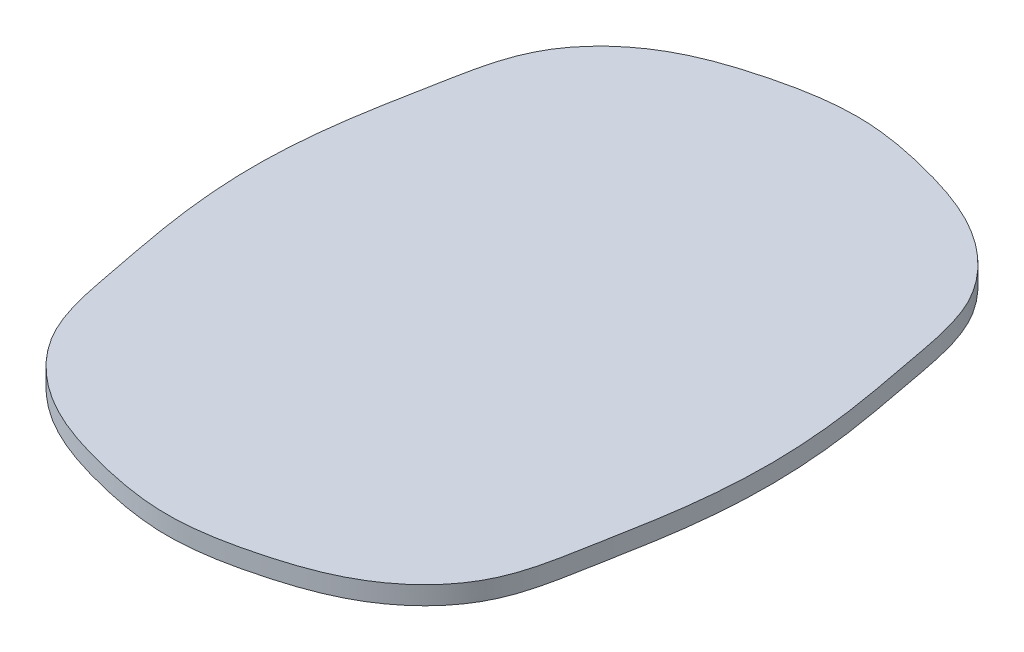
SolidWorks part; units mm, degrees
ref_plane "Front Plane" through (0, 0, 0) normal (0, 0, 1) x (1, 0, 0)
ref_plane "Top Plane" through (0, 0, 0) normal (0, 1, 0) x (1, 0, 0)
ref_plane "Right Plane" through (0, 0, 0) normal (1, 0, 0) x (0, 0, -1)
sketch "Sketch2" plane through (0, 0, 0) normal (0, 1, 0) x (1, 0, 0)
  line L1 (0, 188.5) -> (0, 0) construction
  line L2 (-44.5, 181.8105) -> (44.5, 181.8105) construction
  line L9 (-141, -0.3435) -> (141, 0.3435) construction
  line L10 (-86.25, 165.0195) -> (86.25, 165.0195) construction
  line L11 (-117.5, 132.6399) -> (117.5, 132.6399) construction
  line L12 (-130, 89.4108) -> (130, 89.4108) construction
  line L13 (-137.75, 45.0832) -> (137.75, 45.0832) construction
  spline S0 degree 3 poles (-44.8234, 182.8439) (0, 191.3281) (44.8235, 182.8439) (87.7059, 168.1591) (121.8529, 134.6364) (129.8824, 89.1345) (138.6083, 45.3367) (142.1392, 0.3463) (138.8275, -44.6608) (130.3152, -88.5006) (122.5075, -134.0411) (88.5242, -167.7298) (45.7139, -182.6233) (0.9322, -191.3258) (-43.932, -183.0601) (-86.8858, -168.5845) (-121.1942, -135.2286) (-129.4512, -89.7661) (-138.4138, -45.7899) (-142.2452, -0.3465) (-138.6353, 45.115) (-129.887, 89.1343) (-121.8517, 134.6365) (-87.7062, 168.1591) (-44.8234, 182.8439) (0, 191.3281) (44.8235, 182.8439) knots -0.124907 -0.083272 -0.041636 0 0.041636 0.083272 0.124907 0.166543 0.208179 0.249683 0.291187 0.332823 0.374459 0.416094 0.45773 0.499366 0.541002 0.582638 0.624273 0.665909 0.707545 0.749683 0.791821 0.833457 0.875093 0.916728 0.958364 1 1.041636 1.083272 1.124907 only from (0, 188.5) to (0, 188.5)
  point P4 (0, 181.8105)
  point P7 (0, 0)
  point P8 (141, 0.3435)
  point P9 (-141, -0.3435)
  point P11 (44.5, 181.8105)
  point P14 (86.25, 165.0195)
  point P15 (0, 165.0195)
  point P16 (117.5, 132.6399)
  point P17 (130, 89.4108)
  point P18 (-44.5, 181.8105)
  point P19 (-86.25, 165.0195)
  point P20 (-117.5, 132.6399)
  point P23 (0, 132.6399)
  point P24 (137.75, 45.0832)
  point P25 (-130, 89.4108)
  point P26 (-137.75, 45.0832)
  point P27 (0, 188.5)
  point P30 (0, 89.4108)
  point P33 (0, 45.0832)
  point P34 (137.968, -44.4115)
  point P35 (130.4341, -88.7763)
  point P36 (118.1449, -132.0658)
  point P37 (87.053, -164.5972)
  point P38 (45.3853, -181.5915)
  point P39 (0.9185, -188.4978)
  point P40 (-43.6136, -182.0251)
  point P41 (-85.4449, -165.4378)
  point P42 (-116.8523, -133.2108)
  point P43 (-129.5628, -90.0432)
  point P44 (-137.5287, -45.7539)
  dimension "D3" = 282
  dimension "D2" = 188.5
  dimension "D5" = 45
  dimension "D6" = 45
  dimension "D1" = 89
  dimension "D4" = 172.5
  dimension "D7" = 45
  dimension "D8" = 235
  dimension "D9" = 45
  dimension "D10" = 260
  dimension "D11" = 45
  dimension "D12" = 275.5
extrude "MainBody" add sketch "Sketch2" along normal blind 10
equation "\"MajorAxis\"= 377mm"
equation "\"MinorAxis\"= 282mm"
equation "\"MajorDiagonal\"= 353mm"
equation "\"SlotSpacing\"= 45mm"
equation "\"SlotRadius\"=5"
equation "\"D3@Sketch2\"=\"MinorAxis\""
equation "\"D2@Sketch2\"=\"MajorAxis\" / 2"
equation "\"D5@Sketch2\"=\"SlotSpacing\""
equation "\"D7@Sketch2\"=\"SlotSpacing\""
equation "\"D9@Sketch2\"=\"SlotSpacing\""
equation "\"D11@Sketch2\"=\"SlotSpacing\""
